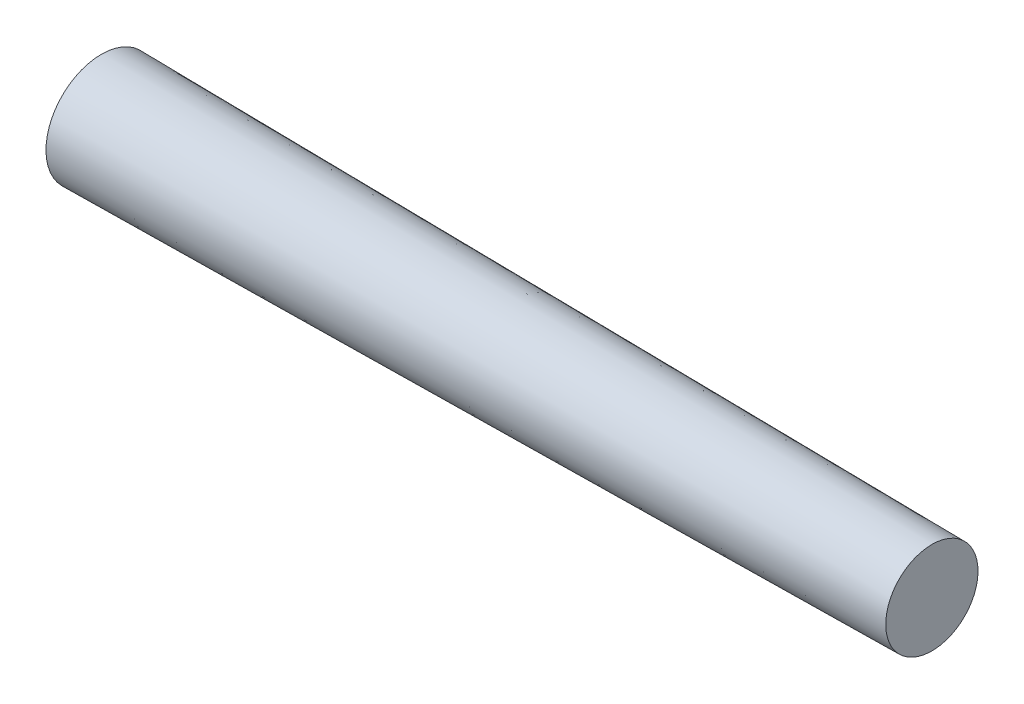
SolidWorks part; units mm, degrees
material "Plain Carbon Steel"
ref_plane "Front Plane" through (0, 0, 0) normal (0, 0, 1) x (1, 0, 0)
ref_plane "Top Plane" through (0, 0, 0) normal (0, 1, 0) x (1, 0, 0)
ref_plane "Right Plane" through (0, 0, 0) normal (1, 0, 0) x (0, 0, -1)
sketch "Sketch1" plane through (0, 0, 0) normal (0, 0, 1) x (1, 0, 0)
  line L0 (0, 0) -> (45, 0) construction
  line L1 (0, 0) -> (0, 3)
  line L2 (0, 3) -> (45, 2.5)
  line L3 (45, 2.5) -> (45, 0)
  line L4 (45, 0) -> (0, 0)
  dimension "D1" = 45
  dimension "D2" = 3
  dimension "D3" = 2.5
revolve "Revolve1" add sketch "Sketch1" angle 360 about L0
